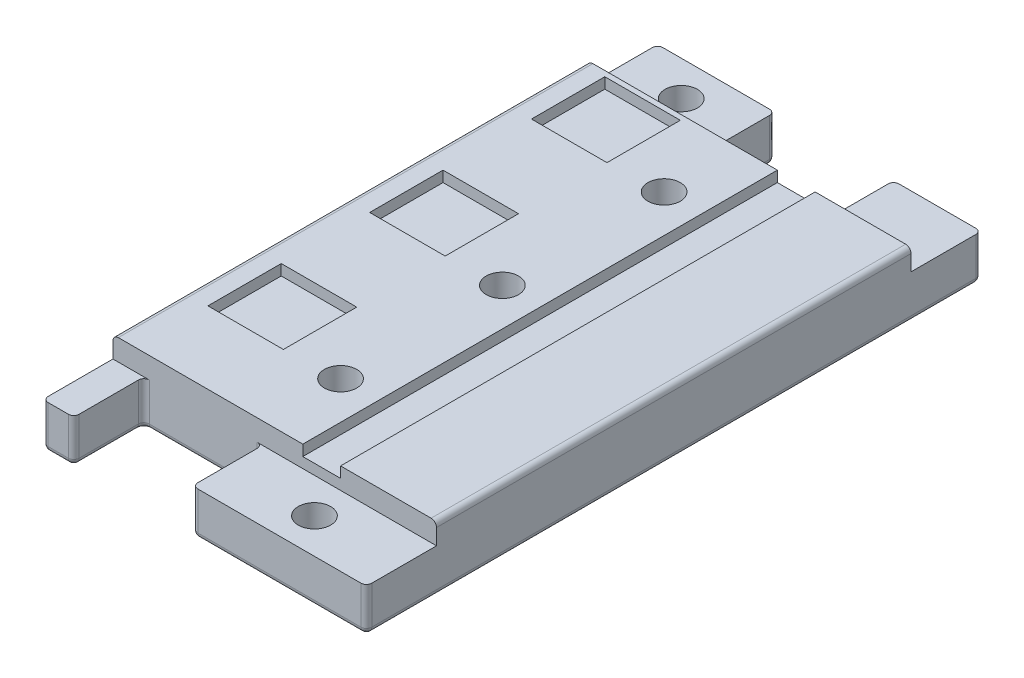
SolidWorks part; units mm, degrees
ref_plane "Front Plane" through (0, 0, 0) normal (0, 0, 1) x (1, 0, 0)
ref_plane "Top Plane" through (0, 0, 0) normal (0, 1, 0) x (1, 0, 0)
ref_plane "Right Plane" through (0, 0, 0) normal (1, 0, 0) x (0, 0, -1)
sketch "Sketch2" plane through (0, 1.9682, 0) normal (0, -1, 0) x (-1, 0, 0)
  line L1 (-30, -22) -> (0, -22)
  line L2 (-30, -22) -> (-30, 22)
  line L3 (-30, 22) -> (0, 22)
  line L4 (0, -22) -> (0, 22)
  line L6 (-30, -23) -> (-30, 23) construction
  line L7 (-21.1048, 22) -> (9.8952, 22) construction
  line L8 (9.8952, -22) -> (-21.1048, -22) construction
extrude "Boss-Extrude1" add sketch "Sketch2" along normal blind 6
sketch "Sketch4" plane through (0, -4.0318, 0) normal (0, -1, 0) x (-1, 0, 0)
  line L0 (-14.8794, 26.6064) -> (-10.8794, 26.6064) construction
  line L1 (0, 22) -> (-10.8794, 22)
  line L2 (0, 22) -> (0, 28.5)
  line L3 (0, 28.5) -> (-10.8794, 28.5)
  line L4 (-10.8794, 22) -> (-10.8794, 28.5)
  line L5 (-30, 22) -> (-21.8794, 22)
  line L6 (-30, 22) -> (-30, 28.5)
  line L7 (-30, 28.5) -> (-21.8794, 28.5)
  line L8 (-21.8794, 22) -> (-21.8794, 28.5)
  line L9 (0, -22) -> (-2.8674, -22)
  line L10 (0, -22) -> (0, -28.5)
  line L11 (0, -28.5) -> (-2.8674, -28.5)
  line L12 (-2.8674, -22) -> (-2.8674, -28.5)
  line L13 (-30, -22) -> (-13.8674, -22)
  line L14 (-30, -22) -> (-30, -28.5)
  line L15 (-30, -28.5) -> (-13.8674, -28.5)
  line L16 (-13.8674, -22) -> (-13.8674, -28.5)
  line L17 (-17.8794, 26.6064) -> (-21.8794, 26.6064) construction
  line L18 (-6.8674, -27.0854) -> (-2.8674, -27.0854) construction
  line L20 (-9.8674, -27.0854) -> (-13.8674, -27.0854) construction
  circle A0 centre (-16.3794, 26.6064) radius 1.5 construction
  circle A1 centre (-8.3674, -27.0854) radius 1.5 construction
  dimension "D1" = 4
  dimension "D2" = 6.5
  dimension "D3" = 6.5
extrude "Boss-Extrude2" add sketch "Sketch4" against normal up to surface (4.0318 mm away)
sketch "Sketch3" plane through (0, 1.9682, 0) normal (0, -1, 0) x (-1, 0, 0)
  line L1 (-21.1048, -22) -> (-17.6048, -22)
  line L2 (-21.1048, -22) -> (-21.1048, 22)
  line L3 (-21.1048, 22) -> (-17.6048, 22)
  line L4 (-17.6048, -22) -> (-17.6048, 22)
  line L5 (9.8952, -22) -> (-21.1048, -22) construction
  line L6 (-9.1048, 6.5) -> (-2.1048, 6.5)
  line L7 (-9.1048, 6.5) -> (-9.1048, -0.3)
  line L8 (-9.1048, -0.3) -> (-2.1048, -0.3)
  line L9 (-2.1048, 6.5) -> (-2.1048, -0.3)
  line L10 (-9.1048, -8.5) -> (-2.1048, -8.5)
  line L11 (-9.1048, -8.5) -> (-9.1048, -15.3)
  line L12 (-9.1048, -15.3) -> (-2.1048, -15.3)
  line L13 (-2.1048, -8.5) -> (-2.1048, -15.3)
  line L14 (-9.1048, 21.5) -> (-2.1048, 21.5)
  line L15 (-9.1048, 21.5) -> (-9.1048, 14.7)
  line L16 (-9.1048, 14.7) -> (-2.1048, 14.7)
  line L17 (-2.1048, 21.5) -> (-2.1048, 14.7)
  line L18 (-21.1048, 22) -> (9.8952, 22) construction
  line L19 (-21.1048, -7) -> (-21.1048, 7) construction
  dimension "D1" = 3.5
extrude "Cut-Extrude3" cut sketch "Sketch3" along normal blind 1
fillet "Fillet1" radius 0.5 24 edges at (25.9397, -4.0318, -28.5) (21.8794, -4.0318, -25.25) (16.3794, -4.0318, -22) (10.8794, -4.0318, -25.25) (5.4397, -4.0318, -28.5) (0, -4.0318, 0) (1.4337, -4.0318, 28.5) (2.8674, -4.0318, 25.25) (8.3674, -4.0318, 22) (13.8674, -4.0318, 25.25) (21.9337, -4.0318, 28.5) (30, -4.0318, 0) (21.8794, -2.0159, -28.5) (10.8794, -2.0159, -28.5) (30, -2.0159, -28.5) (30, 1.9682, 0) (30, -2.0159, 28.5) (13.8674, -2.0159, 28.5) (13.8674, -2.0159, 22) (2.8674, -2.0159, 22) (2.8674, -2.0159, 28.5) (0, -2.0159, 28.5) (0, -2.0159, -28.5) (0, 1.9682, 0)
sketch "Sketch5" plane through (0, -4.0318, 0) normal (0, -1, 0) x (-1, 0, 0)
  line L0 (-21.9337, -22) -> (-21.9337, -28.5) construction
  line L1 (-30, -22) -> (-13.8674, -22) construction
  line L2 (-30, -28.5) -> (-13.8674, -28.5) construction
  line L3 (-5.4397, 22) -> (-5.4397, 28.5) construction
  line L4 (0, 22) -> (-10.8794, 22) construction
  line L5 (0, 28.5) -> (-10.8794, 28.5) construction
  circle A0 centre (-5.4397, 25.25) radius 1.5
  circle A1 centre (-21.9337, -25.25) radius 1.5
  dimension "D1" = 3
  dimension "D2" = 3
extrude "Cut-Extrude4" cut sketch "Sketch5" against normal up to surface (4.0318 mm away)
sketch "Sketch6" plane through (0, -4.0318, 0) normal (0, -1, 0) x (1, 0, 0)
  circle A0 centre (14.1048, -15) radius 1.5 construction
  circle A1 centre (14.1048, 0) radius 1.5 construction
  circle A2 centre (14.1048, 15) radius 1.5 construction
  circle A3 centre (14.1048, -15) radius 1.5
  circle A4 centre (14.1048, 0) radius 1.5
  circle A5 centre (14.1048, 15) radius 1.5
extrude "Cut-Extrude5" cut sketch "Sketch6" against normal up to surface (6 mm away) up to face at (25.3024, 1.9682, 0)
